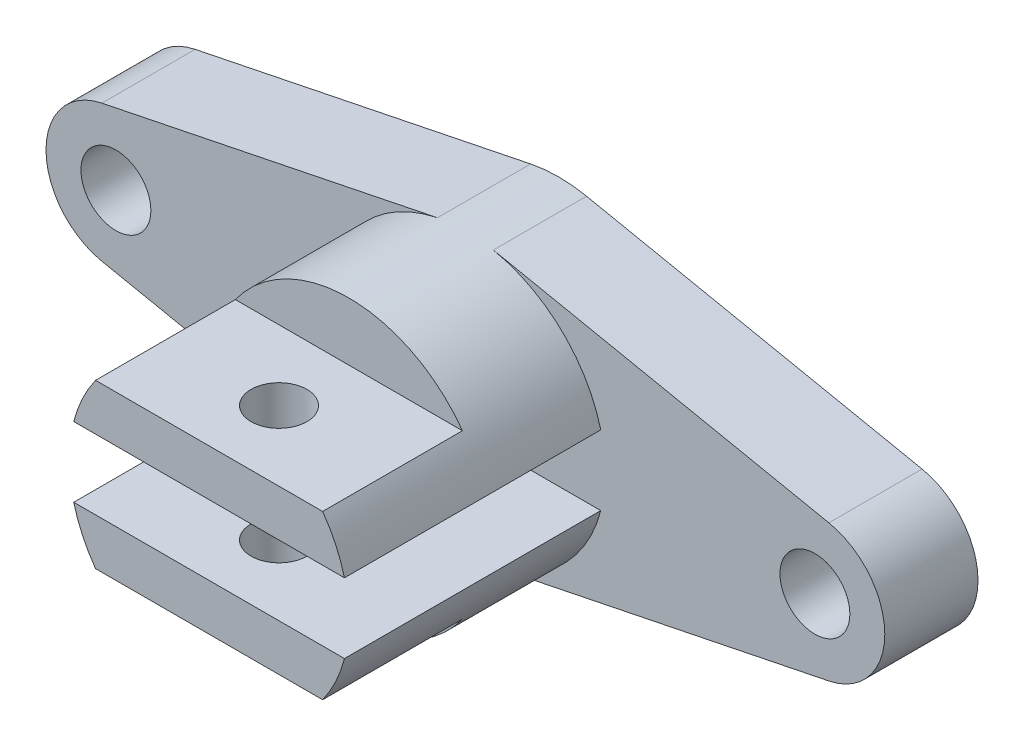
SolidWorks part; units mm, degrees
ref_plane "Alzado" through (0, 0, 0) normal (0, 0, 1) x (1, 0, 0)
ref_plane "Planta" through (0, 0, 0) normal (0, 1, 0) x (1, 0, 0)
ref_plane "Vista lateral" through (0, 0, 0) normal (1, 0, 0) x (0, 0, -1)
sketch "Croquis9" plane through (0, 0, 0) normal (0, 0, 1) x (1, 0, 0)
  line L1 (-78, 14.6969) -> (-6, 29.3939)
  line L2 (-78, -14.6969) -> (-6, -29.3939)
  line L3 (6, 29.3939) -> (78, 14.6969)
  line L4 (78, -14.6969) -> (6, -29.3939)
  circle A1 centre (-75, 0) radius 7.5
  circle A2 centre (75, 0) radius 7.5
  arc A3 (-78, 14.6969) -> (-78, -14.6969) centre (-75, 0) ccw
  arc A4 (78, -14.6969) -> (78, 14.6969) centre (75, 0) ccw
  arc A6 (6, 29.3939) -> (-6, 29.3939) centre (0, 0) ccw
  arc A7 (-6, -29.3939) -> (6, -29.3939) centre (0, 0) ccw
  circle A8 centre (0, 0) radius 30
  dimension "D2" = 15
  dimension "D5" = 30
  dimension "D4" = 150
sketch "Croquis10" plane through (0, 0, 0) normal (0, 0, 1) x (1, 0, 0)
  line L1 (-78, 14.6969) -> (-6, 29.3939)
  line L2 (-78, -14.6969) -> (-6, -29.3939)
  line L3 (6, 29.3939) -> (78, 14.6969)
  line L4 (78, -14.6969) -> (6, -29.3939)
  line L5 (-29.0474, 7.5) -> (29.0474, 7.5)
  line L6 (-29.0474, -7.5) -> (29.0474, -7.5)
  circle A1 centre (-75, 0) radius 7.5
  circle A2 centre (75, 0) radius 7.5
  arc A3 (-78, 14.6969) -> (-78, -14.6969) centre (-75, 0) ccw
  arc A4 (78, -14.6969) -> (78, 14.6969) centre (75, 0) ccw
  arc A6 (6, 29.3939) -> (-6, 29.3939) centre (0, 0) ccw
  arc A7 (-6, -29.3939) -> (6, -29.3939) centre (0, 0) ccw
  arc A9 (-29.0474, -7.5) -> (29.0474, -7.5) centre (0, 0) ccw
  arc A10 (29.0474, 7.5) -> (-29.0474, 7.5) centre (0, 0) ccw
  dimension "D1" = 7.5
  dimension "D2" = 15
  dimension "D3" = 7.5
  dimension "D5" = 30
  dimension "D4" = 150
sketch "Croquis11" plane through (0, 0, 0) normal (0, 0, 1) x (1, 0, 0)
  line L1 (-78, 14.6969) -> (-6, 29.3939)
  line L2 (-78, -14.6969) -> (-6, -29.3939)
  line L3 (6, 29.3939) -> (78, 14.6969)
  line L4 (78, -14.6969) -> (6, -29.3939)
  line L5 (-24.367, 17.5) -> (24.367, 17.5)
  line L7 (-24.367, -17.5) -> (24.367, -17.5)
  line L8 (-29.0474, 7.5) -> (29.0474, 7.5)
  line L9 (-29.0474, -7.5) -> (29.0474, -7.5)
  circle A1 centre (-75, 0) radius 7.5
  circle A2 centre (75, 0) radius 7.5
  arc A3 (-78, 14.6969) -> (-78, -14.6969) centre (-75, 0) ccw
  arc A4 (78, -14.6969) -> (78, 14.6969) centre (75, 0) ccw
  arc A6 (6, 29.3939) -> (-6, 29.3939) centre (0, 0) ccw
  arc A7 (-6, -29.3939) -> (6, -29.3939) centre (0, 0) ccw
  arc A10 (-29.0474, -7.5) -> (-24.367, -17.5) centre (0, 0) ccw
  arc A11 (29.0474, 7.5) -> (24.367, 17.5) centre (0, 0) ccw
  arc A12 (-24.367, 17.5) -> (-29.0474, 7.5) centre (0, 0) ccw
  arc A13 (6, 29.3939) -> (-6, 29.3939) centre (0, 0) ccw
  arc A14 (24.367, -17.5) -> (29.0474, -7.5) centre (0, 0) ccw
  arc A15 (-6, -29.3939) -> (6, -29.3939) centre (0, 0) ccw
  dimension "D1" = 17.5
  dimension "D2" = 15
  dimension "D3" = 17.5
  dimension "D5" = 30
  dimension "D4" = 150
extrude "Saliente-Extruir1" add sketch "Croquis9" along normal blind 20 contours L3 A4 L4 A7 L2 A3 L1 A6
extrude "Cortar-Extruir1" cut sketch "Croquis9<8>" along normal blind 20 contours A1
sketch "Croquis9<8>" plane through (0, 0, 0) normal (0, 0, 1) x (1, 0, 0) same geometry as "Croquis9"
extrude "Cortar-Extruir2" cut sketch "Croquis9<10>" along normal blind 20 contours A2
sketch "Croquis9<10>" plane through (0, 0, 0) normal (0, 0, 1) x (1, 0, 0) same geometry as "Croquis9"
extrude "Saliente-Extruir2" add sketch "Croquis10" along normal blind 45 contours L5 A10 | L6 A9
extrude "Saliente-Extruir3" add sketch "Croquis11" along normal blind 75 contours L8 A11 L5 A12 | L9 A14 L7 A10
sketch "Croquis12" plane through (0, 0, 0) normal (0, 1, 0) x (1, 0, 0)
  line L0 (-90, 0) -> (-90, -20) construction
  circle A0 centre (0, -60) radius 6
  dimension "D1" = 12
  dimension "D2" = 90
  dimension "D3" = 60
extrude "Cortar-Extruir4" cut sketch "Croquis12" against normal blind 52 and the other way blind 61
